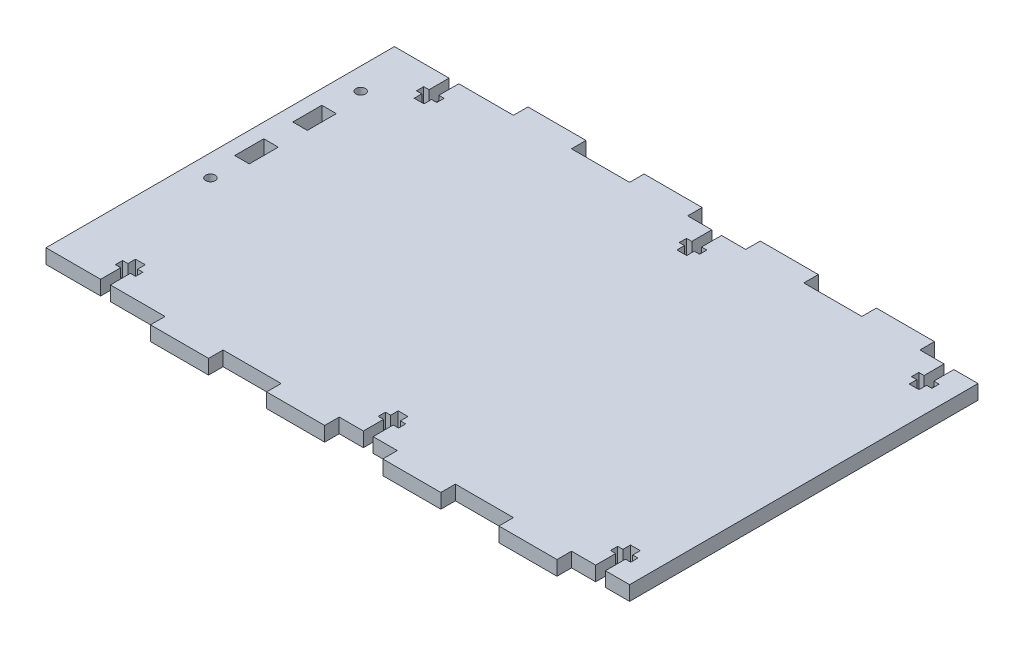
SolidWorks part; units mm, degrees
ref_plane "Front Plane" through (0, 0, 0) normal (0, 0, 1) x (1, 0, 0)
ref_plane "Top Plane" through (0, 0, 0) normal (0, 1, 0) x (1, 0, 0)
ref_plane "Right Plane" through (0, 0, 0) normal (1, 0, 0) x (0, 0, -1)
sketch "Sketch1" plane through (0, 0, 0) normal (0, 0, 1) x (1, 0, 0)
  line L0 (115.91, -15.875) -> (115.91, 155.575) construction
  line L1 (-139.3499, 155.575) -> (115.91, 155.575)
  line L2 (-139.3499, 155.575) -> (-139.3499, 149.225)
  line L3 (-139.3499, 149.225) -> (115.91, 149.225)
  line L4 (115.91, 155.575) -> (115.91, 149.225)
  dimension "D1" = 6.35
extrude "Boss-Extrude1" add sketch "Sketch1" along normal blind 152.4
sketch "Sketch2" plane through (0, 155.575, 0) normal (0, 1, 0) x (1, 0, 0)
  line L0 (90.51, 0) -> (90.51, 6.35)
  line L1 (115.91, 0) -> (-139.3499, 0) construction
  line L2 (-139.3499, 6.35) -> (-87.29, 6.35) construction
  line L3 (90.51, 6.35) -> (65.11, 6.35)
  line L4 (65.11, 6.35) -> (65.11, 0)
  line L5 (115.91, 0) -> (90.51, 0)
  line L6 (90.51, 0) -> (65.11, 0)
  line L9 (115.91, 0) -> (-139.3499, 0)
  line L10 (-139.3499, 0) -> (-139.3499, -152.4)
  line L11 (-139.3499, -152.4) -> (115.91, -152.4)
  line L12 (115.91, -152.4) -> (115.91, 0)
  line L13 (65.11, 0) -> (-139.3499, 0)
  line L14 (-139.3499, 0) -> (-139.3499, -152.4)
  line L15 (-139.3499, -152.4) -> (115.91, -152.4)
  line L16 (115.91, -152.4) -> (115.91, 0)
  line M7 (115.91, 0) -> (-139.3499, 0)
  dimension "D1" = 25.4
  dimension "D2" = 25.4
  dimension "D3" = 0
extrude "Boss-Extrude2" add sketch "Sketch2" against normal blind 6.35 contours L3 L4 L0 M7 region at (77.81, 155.575, -3.175)
pattern_linear "LPattern1" count 4 spacing 50.8 along (-1, 0, 0) of "Boss-Extrude2"
sketch "Sketch3" plane through (0, 0, 152.4) normal (0, 0, 1) x (1, 0, 0)
  line L0 (115.91, 155.575) -> (-139.3499, 155.575) construction
  line L1 (90.51, 155.575) -> (65.11, 155.575)
  line L2 (90.51, 155.575) -> (90.51, 149.225)
  line L3 (90.51, 149.225) -> (65.11, 149.225)
  line L4 (65.11, 155.575) -> (65.11, 149.225)
  line L5 (-139.3499, 149.225) -> (115.91, 149.225) construction
  dimension "D1" = 25.4
  dimension "D2" = 25.4
extrude "Boss-Extrude3" add sketch "Sketch3" along normal blind 6.35
pattern_linear "LPattern2" count 4 spacing 50.8 along (-1, 0, 0) of "Boss-Extrude3"
sketch "Sketch4" plane through (0, 155.575, 0) normal (0, 1, 0) x (1, 0, 0)
  line L0 (-139.3499, 0) -> (-87.29, 0) construction
  line L1 (90.51, 0) -> (115.91, 0) construction
  line L2 (-113.3199, 0) -> (-113.3199, -13.6148) construction
  line L3 (-87.29, 0) -> (-139.3499, 0) construction
  line L4 (1.61, 0) -> (1.61, -16.5479) construction
  line L5 (14.31, 0) -> (-11.09, 0) construction
  line L6 (103.21, 0) -> (103.21, -21.5198) construction
  line L7 (115.91, 0) -> (90.51, 0) construction
  line L8 (103.21, -152.4) -> (103.21, -137.4626) construction
  line L9 (115.91, -152.4) -> (90.51, -152.4) construction
  line L10 (1.61, -152.4) -> (1.61, -137.4626) construction
  line L11 (14.31, -152.4) -> (-11.09, -152.4) construction
  line L12 (-113.3199, -152.4) -> (-113.3199, -137.4626) construction
  line L13 (-87.29, -152.4) -> (-139.3499, -152.4) construction
  line L14 (-139.3499, -152.4) -> (-87.29, -152.4) construction
  line L15 (-11.09, -152.4) -> (14.31, -152.4) construction
  line B0 (-111.1863, 0) -> (-115.4535, 0)
  line B1 (-115.4535, -11.938) -> (-117.7649, -11.938)
  line B2 (-117.7649, -11.938) -> (-117.7649, -8.763)
  line B3 (-117.7649, -8.763) -> (-115.4535, -8.763)
  line B4 (-115.4535, -8.763) -> (-115.4535, 0)
  line B5 (-115.4535, -11.938) -> (-115.4535, -15.24)
  line B6 (-115.4535, -15.24) -> (-111.1863, -15.24)
  line B7 (-111.1863, -11.938) -> (-111.1863, -15.24)
  line B8 (-111.1863, -8.763) -> (-111.1863, 0)
  line B9 (-108.8749, -8.763) -> (-111.1863, -8.763)
  line B10 (-108.8749, -11.938) -> (-108.8749, -8.763)
  line B11 (-111.1863, -11.938) -> (-108.8749, -11.938)
  line B12 (3.7436, 0) -> (-0.5236, 0)
  line B13 (-0.5236, -11.938) -> (-2.835, -11.938)
  line B14 (-2.835, -11.938) -> (-2.835, -8.763)
  line B15 (-2.835, -8.763) -> (-0.5236, -8.763)
  line B16 (-0.5236, -8.763) -> (-0.5236, 0)
  line B17 (-0.5236, -11.938) -> (-0.5236, -15.24)
  line B18 (-0.5236, -15.24) -> (3.7436, -15.24)
  line B19 (3.7436, -11.938) -> (3.7436, -15.24)
  line B20 (3.7436, -8.763) -> (3.7436, 0)
  line B21 (6.055, -8.763) -> (3.7436, -8.763)
  line B22 (6.055, -11.938) -> (6.055, -8.763)
  line B23 (3.7436, -11.938) -> (6.055, -11.938)
  line B24 (105.3436, 0) -> (101.0764, 0)
  line B25 (101.0764, -11.938) -> (98.765, -11.938)
  line B26 (98.765, -11.938) -> (98.765, -8.763)
  line B27 (98.765, -8.763) -> (101.0764, -8.763)
  line B28 (101.0764, -8.763) -> (101.0764, 0)
  line B29 (101.0764, -11.938) -> (101.0764, -15.24)
  line B30 (101.0764, -15.24) -> (105.3436, -15.24)
  line B31 (105.3436, -11.938) -> (105.3436, -15.24)
  line B32 (105.3436, -8.763) -> (105.3436, 0)
  line B33 (107.655, -8.763) -> (105.3436, -8.763)
  line B34 (107.655, -11.938) -> (107.655, -8.763)
  line B35 (105.3436, -11.938) -> (107.655, -11.938)
  line B36 (-115.4535, -152.4) -> (-111.1863, -152.4)
  line B37 (-111.1863, -140.462) -> (-108.8749, -140.462)
  line B38 (-108.8749, -140.462) -> (-108.8749, -143.637)
  line B39 (-108.8749, -143.637) -> (-111.1863, -143.637)
  line B40 (-111.1863, -143.637) -> (-111.1863, -152.4)
  line B41 (-111.1863, -140.462) -> (-111.1863, -137.16)
  line B42 (-111.1863, -137.16) -> (-115.4535, -137.16)
  line B43 (-115.4535, -140.462) -> (-115.4535, -137.16)
  line B44 (-115.4535, -143.637) -> (-115.4535, -152.4)
  line B45 (-117.7649, -143.637) -> (-115.4535, -143.637)
  line B46 (-117.7649, -140.462) -> (-117.7649, -143.637)
  line B47 (-115.4535, -140.462) -> (-117.7649, -140.462)
  line B48 (-0.5236, -152.4) -> (3.7436, -152.4)
  line B49 (3.7436, -140.462) -> (6.055, -140.462)
  line B50 (6.055, -140.462) -> (6.055, -143.637)
  line B51 (6.055, -143.637) -> (3.7436, -143.637)
  line B52 (3.7436, -143.637) -> (3.7436, -152.4)
  line B53 (3.7436, -140.462) -> (3.7436, -137.16)
  line B54 (3.7436, -137.16) -> (-0.5236, -137.16)
  line B55 (-0.5236, -140.462) -> (-0.5236, -137.16)
  line B56 (-0.5236, -143.637) -> (-0.5236, -152.4)
  line B57 (-2.835, -143.637) -> (-0.5236, -143.637)
  line B58 (-2.835, -140.462) -> (-2.835, -143.637)
  line B59 (-0.5236, -140.462) -> (-2.835, -140.462)
  line B60 (101.0764, -152.4) -> (105.3436, -152.4)
  line B61 (105.3436, -140.462) -> (107.655, -140.462)
  line B62 (107.655, -140.462) -> (107.655, -143.637)
  line B63 (107.655, -143.637) -> (105.3436, -143.637)
  line B64 (105.3436, -143.637) -> (105.3436, -152.4)
  line B65 (105.3436, -140.462) -> (105.3436, -137.16)
  line B66 (105.3436, -137.16) -> (101.0764, -137.16)
  line B67 (101.0764, -140.462) -> (101.0764, -137.16)
  line B68 (101.0764, -143.637) -> (101.0764, -152.4)
  line B69 (98.765, -143.637) -> (101.0764, -143.637)
  line B70 (98.765, -140.462) -> (98.765, -143.637)
  line B71 (101.0764, -140.462) -> (98.765, -140.462)
sketch_block_instance "TSlot-1"
sketch_block "TSlot" parameters "D1"=3.302, "D2"=3.175
sketch_block_instance "TSlot-3"
sketch_block_instance "TSlot-4"
sketch_block_instance "TSlot-9"
sketch_block_instance "TSlot-11"
sketch_block_instance "TSlot-12"
extrude "Cut-Extrude1" cut sketch "Sketch4" against normal blind 6.35
sketch "Sketch5" plane through (0, 155.575, 0) normal (0, 1, 0) x (1, 0, 0)
  line L0 (-132.9999, -55.2358) -> (-132.9999, -140.7347) construction
  line L1 (-132.9999, -38.1) -> (-126.6499, -38.1)
  line L2 (-132.9999, -38.1) -> (-132.9999, -50.8)
  line L3 (-132.9999, -50.8) -> (-126.6499, -50.8)
  line L4 (-126.6499, -38.1) -> (-126.6499, -50.8)
  line L5 (-132.9999, -63.5) -> (-126.6499, -63.5)
  line L6 (-132.9999, -63.5) -> (-132.9999, -76.2)
  line L7 (-132.9999, -76.2) -> (-126.6499, -76.2)
  line L8 (-126.6499, -63.5) -> (-126.6499, -76.2)
  line L10 (-139.3499, -152.4) -> (-139.3499, 0) construction
  line L11 (-115.4535, 0) -> (-139.3499, 0) construction
  dimension "D1" = 12.7
  dimension "D2" = 6.35
  dimension "D3" = 6.35
  dimension "D4" = 12.7
  dimension "D5" = 12.7
  dimension "D6" = 6.35
  dimension "D7" = 38.1
extrude "Cut-Extrude2" cut sketch "Sketch5" against normal through all
sketch "Sketch6" plane through (0, 155.575, 0) normal (0, 1, 0) x (1, 0, 0)
  line L0 (-132.9999, -22.1864) -> (-126.6499, -26.4536) construction
  line L1 (-132.9999, -26.4536) -> (-126.6499, -22.1864) construction
  line L2 (-132.9999, -87.8464) -> (-126.6499, -92.1136) construction
  line L3 (-132.9999, -92.1136) -> (-126.6499, -87.8464) construction
  circle A0 centre (-129.8249, -89.98) radius 2.0955
  circle A1 centre (-129.8249, -24.32) radius 2.0955
  dimension "D1" = 4.191
extrude "Cut-Extrude3" cut sketch "Sketch6" against normal through all
